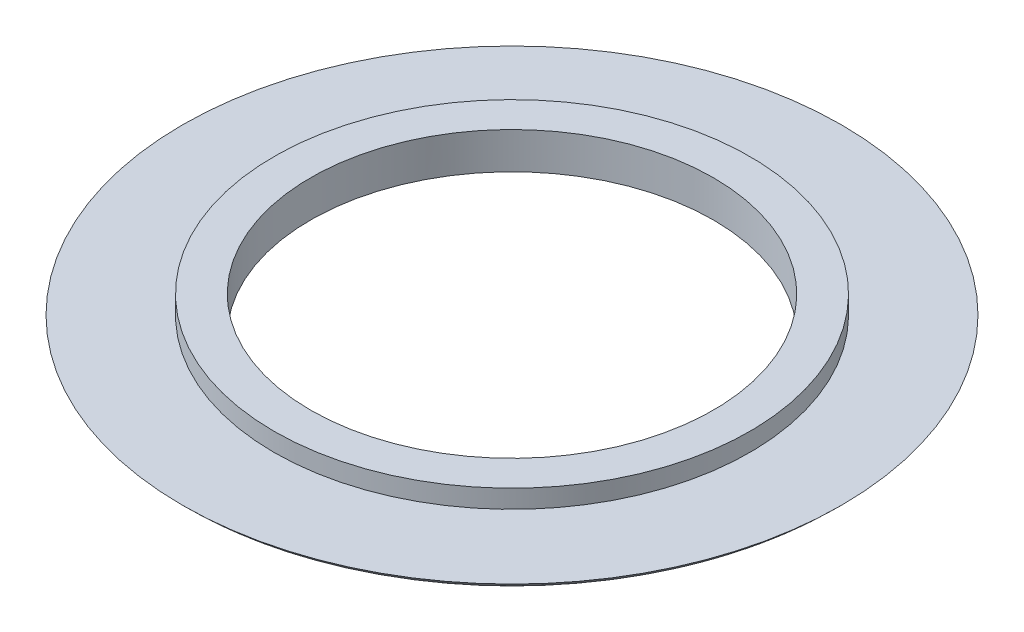
SolidWorks part; units mm, degrees
ref_plane "Спереди" through (0, 0, 0) normal (0, 0, 1) x (1, 0, 0)
ref_plane "Сверху" through (0, 0, 0) normal (0, 1, 0) x (1, 0, 0)
ref_plane "Справа" through (0, 0, 0) normal (1, 0, 0) x (0, 0, -1)
sketch "Эскиз1" plane through (0, 0, 0) normal (0, 1, 0) x (1, 0, 0)
  circle A0 centre (0, 0) radius 13
  circle A1 centre (0, 0) radius 11
  dimension "D1" = 26
  dimension "D2" = 22
extrude "Бобышка-Вытянуть1" add sketch "Эскиз1" along normal blind 1
sketch "Эскиз2" plane through (0, 0, 0) normal (0, -1, 0) x (1, 0, 0)
  circle A1 centre (0, 0) radius 11
  circle A2 centre (0, 0) radius 18
  dimension "D1" = 36
  dimension "D2" = 22
extrude "Бобышка-Вытянуть2" add sketch "Эскиз2" along normal blind 1
fillet "Скругление1" radius 3 1 edges at (0, -1, -18)
